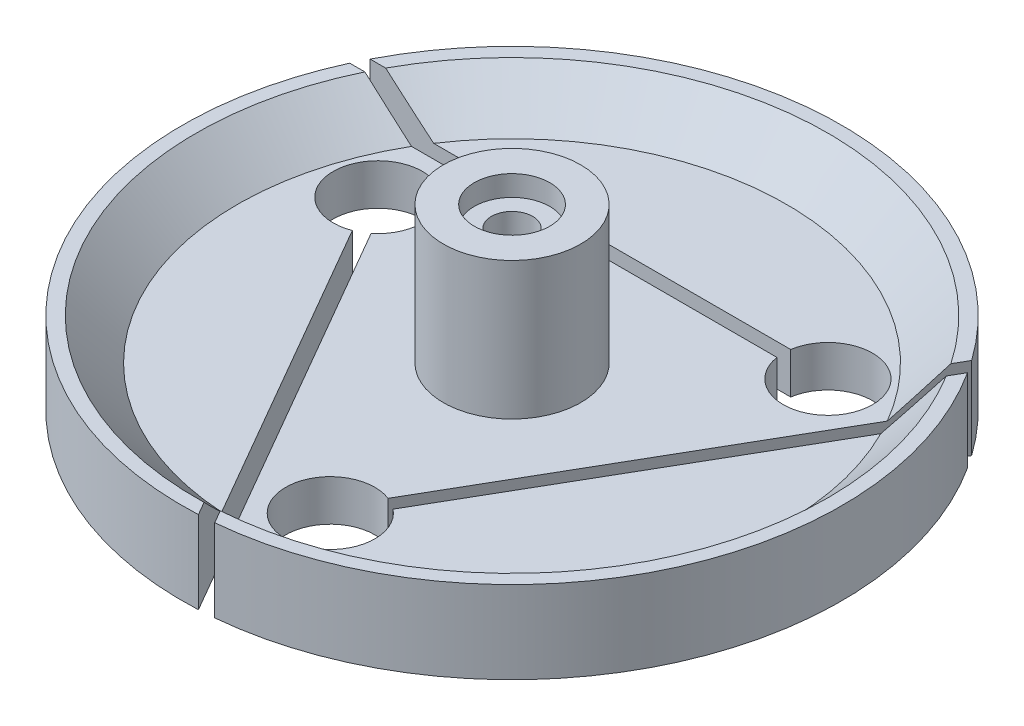
SolidWorks part; units mm, degrees
ref_plane "前视基准面" through (0, 0, 0) normal (0, 0, 1) x (1, 0, 0)
ref_plane "上视基准面" through (0, 0, 0) normal (0, 1, 0) x (1, 0, 0)
ref_plane "右视基准面" through (0, 0, 0) normal (1, 0, 0) x (0, 0, -1)
other "Configuration Table"
sketch "草图2" plane through (0, 0, 0) normal (0, 0, 1) x (1, 0, 0)
  line L0 (0, -31.6818) -> (0, 42.2273) construction
  line L1 (3, 0) -> (48, 0)
  line L2 (48, 0) -> (48, 12)
  line L3 (48, 12) -> (46, 12)
  line L4 (46, 12) -> (40, 6)
  line L5 (40, 6) -> (10, 6)
  line L6 (10, 6) -> (10, 26)
  line L7 (10, 26) -> (5.5, 26)
  line L8 (5.5, 26) -> (5.5, 23)
  line L9 (5.5, 23) -> (3, 23)
  line L10 (3, 23) -> (3, 0)
  line L11 (-9.471, 0) -> (16.701, 0) construction
  dimension "D1" = 3
  dimension "D2" = 10
  dimension "D3" = 3
  dimension "D4" = 5.5
  dimension "D5" = 20
  dimension "D6" = 2
  dimension "D7" = 6
  dimension "D8" = 135
  dimension "D9" = 12
  dimension "D10" = 45
revolve "旋转1" add sketch "草图2" angle 360 about L0
sketch "草图4" plane through (0, 0, 0) normal (0, -1, 0) x (-1, 0, 0)
  line L0 (-59.5813, 0) -> (61.4791, 0) construction
  line L1 (0, -55.1144) -> (0, 61.7008) construction
  line L2 (-18.5, 21) -> (43.1625, 21) construction
  line L3 (-18.5774, 20) -> (43.6348, 20)
  line L4 (-18.5774, 22) -> (42.6615, 22)
  line L5 (-25, 20) -> (48.235, 20) construction
  line L6 (-25, 21) -> (48.235, 21) construction
  line L7 (-25, 22) -> (48.235, 22) construction
  arc A0 (-18.5774, 22) -> (-18.5774, 20) centre (-25, 21) ccw
  arc A1 (43.6348, 20) -> (42.6615, 22) centre (0, 0) ccw
  point P17 (-36.0483, 35.0411)
  point P18 (-46.0522, 48.5464)
  point P19 (-36.7986, 40.8768)
  dimension "D2" = 13
  dimension "D5" = 21
  dimension "D6" = 25
  dimension "D3" = 1
  dimension "D4" = 1
extrude "切除-拉伸1" cut sketch "草图4" against normal blind 15
ref_axis "基准轴1" through (0, 27.3, 0) along (0, -1, 0)
pattern_circular "阵列(圆周)1" count 3 over 360 about axis through (0, 27.3, 0) along (0, -1, 0) of "切除-拉伸1"
